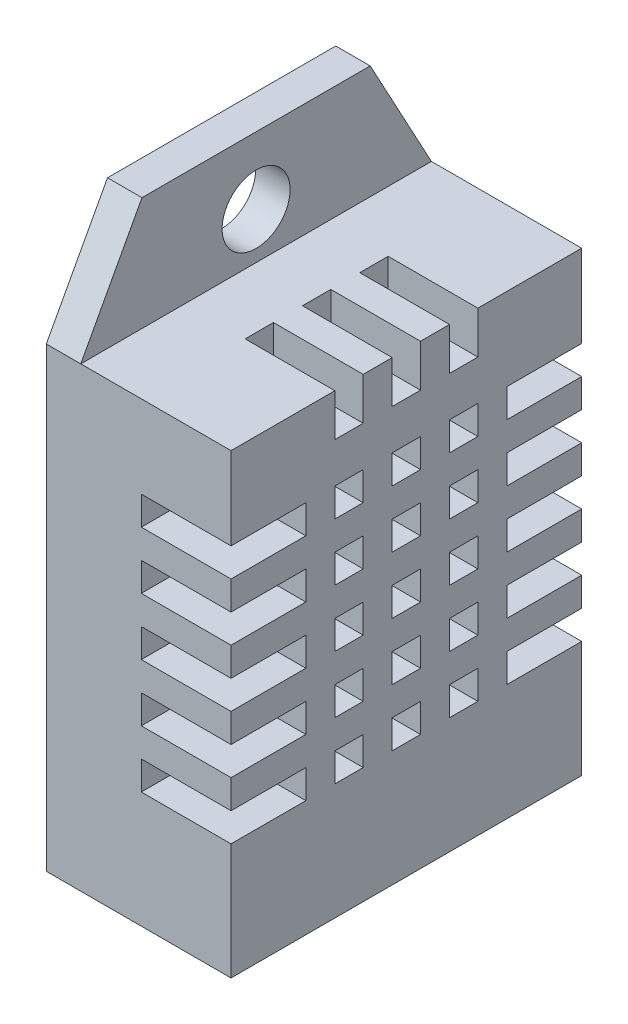
SolidWorks part; units mm, degrees
ref_plane "Front Plane" through (0, 0, 0) normal (0, 0, 1) x (1, 0, 0)
ref_plane "Top Plane" through (0, 0, 0) normal (0, 1, 0) x (1, 0, 0)
ref_plane "Right Plane" through (0, 0, 0) normal (1, 0, 0) x (0, 0, -1)
sketch "Sketch1" plane through (0, 0, 0) normal (1, 0, 0) x (0, 0, -1)
  line L0 (-7.735, 7.575) -> (7.735, 7.575)
  line L1 (-5.035, 12.575) -> (5.035, 12.575)
  line L2 (-7.735, 7.575) -> (-7.735, -12.575)
  line L3 (-7.735, -12.575) -> (7.735, -12.575)
  line L4 (7.735, 7.575) -> (7.735, -12.575)
  line L5 (-6.2972, 10.2376) -> (7.735, -12.575) construction
  line L6 (-7.735, -12.575) -> (6.2972, 10.2376) construction
  line L7 (5.035, 12.575) -> (7.735, 7.575)
  line L8 (0, 12.575) -> (0, -12.575) construction
  line L9 (-5.035, 12.575) -> (-7.735, 7.575)
  circle A0 centre (0, 9.615) radius 1.5
  point P0 (0, 0)
  point P14 (0, 11.115)
  dimension "D1" = 1.46
  dimension "D3" = 5
extrude "Boss-Extrude1" add sketch "Sketch1" along normal blind 8.15 contours L4 L0 L2 L3 region at (0, -2.5, 0)
extrude "Boss-Extrude2" add sketch "Sketch1<4>" along normal blind 1.52 contours L1 L9 L0 L7 region at (0, 9.9978, 6.2419)
sketch "Sketch1<4>" plane through (0, 0, 0) normal (1, 0, 0) x (0, 0, -1) same geometry as "Sketch1"
shell "Shell1" thickness 1.28
sketch "Sketch2" plane through (8.15, 0, 0) normal (1, 0, 0) x (0, 0, -1)
  line L0 (-7.735, 7.575) -> (7.735, 7.575) construction
  line L1 (3.155, 7.575) -> (3.155, 5.705)
  line L2 (-0.625, 7.575) -> (-0.625, 5.705)
  line L3 (-0.625, 5.705) -> (0.625, 5.705)
  line L4 (0.625, 7.575) -> (0.625, 5.705)
  line L5 (0, 7.575) -> (0.625, 5.705) construction
  line L6 (-0.625, 5.705) -> (0, 7.575) construction
  line L7 (1.905, 5.705) -> (3.155, 5.705)
  line L8 (-0.625, 7.575) -> (0.625, 7.575)
  line L9 (1.905, 7.575) -> (1.905, 5.705)
  line L10 (1.905, 7.575) -> (3.155, 7.575)
  line L11 (2.53, 7.575) -> (3.155, 5.705) construction
  line L12 (1.905, 5.705) -> (2.53, 7.575) construction
  line L13 (-1.905, 7.575) -> (-1.905, 5.705)
  line L14 (-3.155, 5.705) -> (-1.905, 5.705)
  line L15 (-3.155, 7.575) -> (-1.905, 7.575)
  line L16 (-2.53, 7.575) -> (-1.905, 5.705) construction
  line L17 (-3.155, 7.575) -> (-3.155, 5.705)
  line L18 (-3.155, 5.705) -> (-2.53, 7.575) construction
  line L19 (-0.625, 3.935) -> (0.625, 3.935)
  line L20 (-3.155, 2.6708) -> (-1.905, 2.6708)
  line L21 (-3.155, 2.6708) -> (-3.155, 3.935)
  line L22 (-3.155, 3.935) -> (-1.905, 3.935)
  line L23 (-1.905, 2.6708) -> (-1.905, 3.935)
  line L24 (-3.155, 2.6708) -> (-1.905, 3.935) construction
  line L25 (-3.155, 3.935) -> (-1.905, 2.6708) construction
  line L26 (-0.625, 2.6708) -> (-0.625, 3.935)
  line L27 (0.625, 2.6708) -> (0.625, 3.935)
  line L28 (-0.625, 2.6708) -> (0.625, 2.6708)
  line L29 (1.905, 3.935) -> (3.155, 3.935)
  line L30 (1.905, 2.6708) -> (1.905, 3.935)
  line L31 (3.155, 2.6708) -> (3.155, 3.935)
  line L32 (1.905, 2.6708) -> (3.155, 2.6708)
  line L33 (-0.625, 1.405) -> (0.625, 1.405)
  line L34 (-0.625, 0.1408) -> (-0.625, 1.405)
  line L35 (0.625, 0.1408) -> (0.625, 1.405)
  line L36 (-0.625, 0.1408) -> (0.625, 0.1408)
  line L37 (1.905, 1.405) -> (3.155, 1.405)
  line L38 (1.905, 0.1408) -> (1.905, 1.405)
  line L39 (3.155, 0.1408) -> (3.155, 1.405)
  line L40 (1.905, 0.1408) -> (3.155, 0.1408)
  line L41 (-0.625, -1.125) -> (0.625, -1.125)
  line L42 (-0.625, -2.3892) -> (-0.625, -1.125)
  line L43 (0.625, -2.3892) -> (0.625, -1.125)
  line L44 (-0.625, -2.3892) -> (0.625, -2.3892)
  line L45 (1.905, -1.125) -> (3.155, -1.125)
  line L46 (1.905, -2.3892) -> (1.905, -1.125)
  line L47 (3.155, -2.3892) -> (3.155, -1.125)
  line L48 (1.905, -2.3892) -> (3.155, -2.3892)
  line L49 (-0.625, -3.655) -> (0.625, -3.655)
  line L50 (-0.625, -4.9192) -> (-0.625, -3.655)
  line L51 (0.625, -4.9192) -> (0.625, -3.655)
  line L52 (-0.625, -4.9192) -> (0.625, -4.9192)
  line L53 (1.905, -3.655) -> (3.155, -3.655)
  line L54 (1.905, -4.9192) -> (1.905, -3.655)
  line L55 (3.155, -4.9192) -> (3.155, -3.655)
  line L56 (1.905, -4.9192) -> (3.155, -4.9192)
  line L57 (-0.625, -6.185) -> (0.625, -6.185)
  line L58 (-0.625, -7.4492) -> (-0.625, -6.185)
  line L59 (0.625, -7.4492) -> (0.625, -6.185)
  line L60 (-0.625, -7.4492) -> (0.625, -7.4492)
  line L61 (1.905, -6.185) -> (3.155, -6.185)
  line L62 (1.905, -7.4492) -> (1.905, -6.185)
  line L63 (3.155, -7.4492) -> (3.155, -6.185)
  line L64 (1.905, -7.4492) -> (3.155, -7.4492)
  line L65 (-3.155, 1.405) -> (-1.905, 1.405)
  line L66 (-3.155, 0.1408) -> (-3.155, 1.405)
  line L67 (-1.905, 0.1408) -> (-1.905, 1.405)
  line L68 (-3.155, 0.1408) -> (-1.905, 0.1408)
  line L69 (-3.155, -1.125) -> (-1.905, -1.125)
  line L70 (-3.155, -2.3892) -> (-3.155, -1.125)
  line L71 (-1.905, -2.3892) -> (-1.905, -1.125)
  line L72 (-3.155, -2.3892) -> (-1.905, -2.3892)
  line L73 (-3.155, -3.655) -> (-1.905, -3.655)
  line L74 (-3.155, -4.9192) -> (-3.155, -3.655)
  line L75 (-1.905, -4.9192) -> (-1.905, -3.655)
  line L76 (-3.155, -4.9192) -> (-1.905, -4.9192)
  line L77 (-3.155, -6.185) -> (-1.905, -6.185)
  line L78 (-3.155, -7.4492) -> (-3.155, -6.185)
  line L79 (-1.905, -7.4492) -> (-1.905, -6.185)
  line L80 (-3.155, -7.4492) -> (-1.905, -7.4492)
  line L81 (-7.7805, 2.6708) -> (-4.435, 3.935) construction
  line L82 (-7.7805, 2.6708) -> (-7.7805, 3.935)
  line L83 (-7.7805, 3.935) -> (-4.435, 2.6708) construction
  line L84 (-7.7805, 3.935) -> (-4.435, 3.935)
  line L85 (-4.435, 2.6708) -> (-4.435, 3.935)
  line L86 (-7.7805, 2.6708) -> (-4.435, 2.6708)
  line L87 (0, 12.575) -> (0, -10.4162) construction
  line L88 (-5.035, 12.575) -> (5.035, 12.575) construction
  line L89 (0, 12.575) -> (0, -12.575) construction
  line L90 (7.7805, 3.935) -> (4.435, 2.6708) construction
  line L91 (7.7805, 2.6708) -> (4.435, 3.935) construction
  line L92 (7.7805, 2.6708) -> (4.435, 2.6708)
  line L93 (4.435, 2.6708) -> (4.435, 3.935)
  line L94 (7.7805, 3.935) -> (4.435, 3.935)
  line L95 (7.7805, 2.6708) -> (7.7805, 3.935)
  line L96 (-7.7805, 1.405) -> (-4.435, 1.405)
  line L97 (-4.435, 0.1408) -> (-4.435, 1.405)
  line L98 (-7.7805, 0.1408) -> (-4.435, 0.1408)
  line L99 (-7.7805, 0.1408) -> (-7.7805, 1.405)
  line L100 (7.7805, 0.1408) -> (4.435, 0.1408)
  line L101 (4.435, 0.1408) -> (4.435, 1.405)
  line L102 (7.7805, 1.405) -> (4.435, 1.405)
  line L103 (7.7805, 0.1408) -> (7.7805, 1.405)
  line L104 (-7.7805, -1.125) -> (-4.435, -1.125)
  line L105 (-4.435, -2.3892) -> (-4.435, -1.125)
  line L106 (-7.7805, -2.3892) -> (-4.435, -2.3892)
  line L107 (-7.7805, -2.3892) -> (-7.7805, -1.125)
  line L108 (7.7805, -2.3892) -> (4.435, -2.3892)
  line L109 (4.435, -2.3892) -> (4.435, -1.125)
  line L110 (7.7805, -1.125) -> (4.435, -1.125)
  line L111 (7.7805, -2.3892) -> (7.7805, -1.125)
  line L112 (-7.7805, -3.655) -> (-4.435, -3.655)
  line L113 (-4.435, -4.9192) -> (-4.435, -3.655)
  line L114 (-7.7805, -4.9192) -> (-4.435, -4.9192)
  line L115 (-7.7805, -4.9192) -> (-7.7805, -3.655)
  line L116 (7.7805, -4.9192) -> (4.435, -4.9192)
  line L117 (4.435, -4.9192) -> (4.435, -3.655)
  line L118 (7.7805, -3.655) -> (4.435, -3.655)
  line L119 (7.7805, -4.9192) -> (7.7805, -3.655)
  line L120 (-7.7805, -6.185) -> (-4.435, -6.185)
  line L121 (-4.435, -7.4492) -> (-4.435, -6.185)
  line L122 (-7.7805, -7.4492) -> (-4.435, -7.4492)
  line L123 (-7.7805, -7.4492) -> (-7.7805, -6.185)
  line L124 (7.7805, -7.4492) -> (4.435, -7.4492)
  line L125 (4.435, -7.4492) -> (4.435, -6.185)
  line L126 (7.7805, -6.185) -> (4.435, -6.185)
  line L127 (7.7805, -7.4492) -> (7.7805, -6.185)
  point P0 (0, 7.575)
  point P2 (2.53, 7.575)
  point P14 (-2.53, 7.575)
  point P20 (-2.53, 4.043)
  point P25 (-5.06, 4.043)
  point P96 (5.06, 4.043)
  line M66 (7.735, -12.575) -> (7.735, 7.575)
  line M67 (7.735, 7.575) -> (-7.735, 7.575)
  line M68 (-7.735, 7.575) -> (-7.735, -12.575)
  dimension "D1" = 1.25
  dimension "D2" = 1.25
  dimension "D3" = 1.77
  dimension "D4" = 3
  dimension "D5" = 5
  dimension "D6" = 5
extrude "Cut-Extrude1" cut sketch "Sketch2" against normal blind 3.96 contours L4 L2 L3 M67 | L9 L7 L1 M67 | L38 L40 L39 L37 | L102 L101 L100 M66 | L94 L93 L92 M66 | L26 L28 L27 L19 | L66 L68 L67 L65 | L20 L23 L22 L21 | L86 L85 L84 M68 | L98 L97 L96 M68 | L106 L105 L104 M68 | L114 L113 L112 M68 | L70 L72 L71 L69 | L42 L44 L43 L41 | L46 L48 L47 L45 | L110 L109 L108 M66 | L118 L117 L116 M66 | L54 L56 L55 L53 | L50 L52 L51 L49 | L74 L76 L75 L73 | L126 L125 L124 M66 | L62 L64 L63 L61 | L78 L80 L79 L77 | L122 L121 L120 M68 | L14 L13 L15 L17 | L31 L29 L30 L32 | L35 L33 L34 L36 | L59 L57 L58 L60 region at (8.15, -6.8171, 6.085) region at (8.15, -4.2871, 6.085) region at (8.15, -1.7571, 6.085) region at (8.15, 0.7729, 6.085) region at (8.15, 3.3029, 6.085) region at (8.15, 6.64, 0) region at (8.15, 6.64, -2.53) region at (8.15, -6.8171, -6.085) region at (8.15, -4.2871, -6.085) region at (8.15, -1.7571, -6.085) region at (8.15, 0.7729, -6.085) region at (8.15, 3.3029, -6.085) region at (8.15, 3.3029, 0) region at (8.15, 3.3029, 2.53) region at (8.15, 0.7729, -2.53) region at (8.15, -1.7571, 0) region at (8.15, -1.7571, -2.53) region at (8.15, -4.2871, 0) region at (8.15, -4.2871, -2.53) region at (8.15, -6.8171, -2.53) region at (8.15, 0.7729, 2.53) region at (8.15, -1.7571, 2.53) region at (8.15, -4.2871, 2.53) region at (8.15, -6.8171, 2.53)
sketch "Sketch3" plane through (0, -12.575, 0) normal (0, -1, 0) x (1, 0, 0)
  line L0 (2.31, 7.735) -> (2.31, -7.735) construction
  line L1 (8.15, 7.735) -> (0, 7.735) construction
  line L2 (8.15, -7.735) -> (0, -7.735) construction
  line L3 (0, 5.035) -> (0, 7.735) construction
  circle A0 centre (2.31, 3.7043) radius 0.15
  circle A1 centre (2.31, 1.1643) radius 0.15
  circle A2 centre (2.31, -1.3757) radius 0.15
  circle A3 centre (2.31, -3.9157) radius 0.15
  dimension "D2" = 4
  dimension "D1" = 2.31
extrude "Boss-Extrude3" add sketch "Sketch3" along normal blind 2.8
sketch "Sketch5" plane through (0, 0, 0) normal (-1, 0, 0) x (0, 0, 1)
  line L0 (-4.0657, -15.375) -> (-3.7657, -15.375) construction
  line L1 (-1.5257, -15.375) -> (-1.2257, -15.375) construction
  line L2 (1.0143, -15.375) -> (1.3143, -15.375) construction
  line L3 (3.5543, -15.375) -> (3.8543, -15.375) construction
  circle A0 centre (-3.9157, -15.375) radius 0.15
  circle A1 centre (-1.3757, -15.375) radius 0.15
  circle A2 centre (1.1643, -15.375) radius 0.15
  circle A3 centre (3.7043, -15.375) radius 0.15
extrude "Boss-Extrude4" add sketch "Sketch5" against normal blind 10
sketch "Sketch6" plane through (10, 0, 0) normal (1, 0, 0) x (0, 0, -1)
  line L1 (-5.9478, -16.5263) -> (6.873, -16.5263)
  line L2 (-5.9478, -16.5263) -> (-5.9478, -14.4445)
  line L3 (-5.9478, -14.4445) -> (6.873, -14.4445)
  line L4 (6.873, -16.5263) -> (6.873, -14.4445)
  line L5 (-5.9478, -16.5263) -> (6.873, -14.4445) construction
  line L6 (-5.9478, -14.4445) -> (6.873, -16.5263) construction
  point P0 (0.4626, -15.4854)
  point P5 (6.873, -14.4445)
extrude "Cut-Extrude2" cut sketch "Sketch6" against normal blind 6.8
